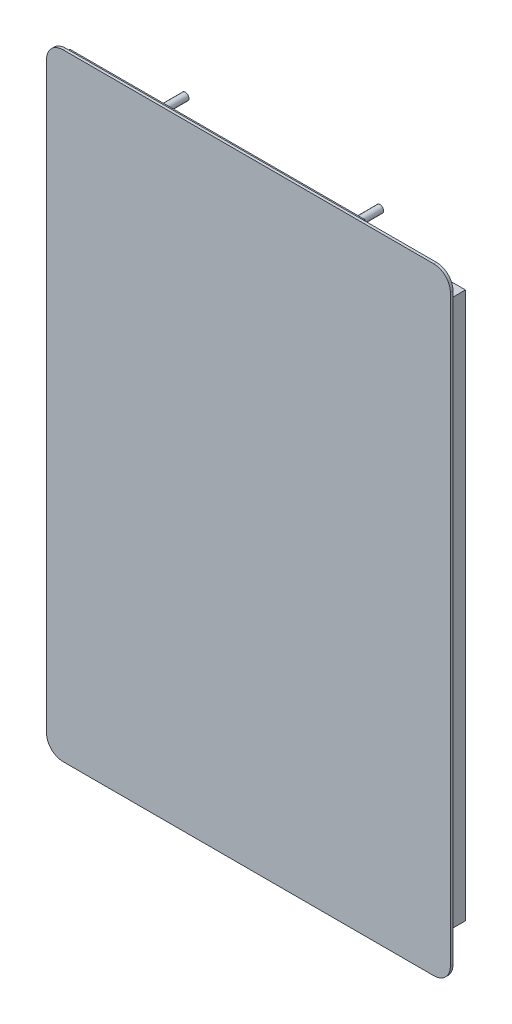
SolidWorks part; units mm, degrees
ref_plane "Front Plane" through (0, 0, 0) normal (0, 0, 1) x (1, 0, 0)
ref_plane "Top Plane" through (0, 0, 0) normal (0, 1, 0) x (1, 0, 0)
ref_plane "Right Plane" through (0, 0, 0) normal (1, 0, 0) x (0, 0, -1)
sketch "Sketch2" plane through (0, 0, 0) normal (0, 0, 1) x (1, 0, 0)
  line L1 (-76.67, -127.5) -> (76.67, -127.5)
  line L2 (-83.5, -120.67) -> (-83.5, 120.67)
  line L3 (-76.67, 127.5) -> (76.67, 127.5)
  line L4 (83.5, -120.67) -> (83.5, 120.67)
  line L5 (-83.5, -127.5) -> (83.5, 127.5) construction
  line L6 (-83.5, 127.5) -> (83.5, -127.5) construction
  arc A0 (76.67, 127.5) -> (83.5, 120.67) centre (76.67, 120.67) cw
  arc A1 (76.67, -127.5) -> (83.5, -120.67) centre (76.67, -120.67) ccw
  arc A2 (-76.67, -127.5) -> (-83.5, -120.67) centre (-76.67, -120.67) cw
  arc A3 (-76.67, 127.5) -> (-83.5, 120.67) centre (-76.67, 120.67) ccw
  point P0 (0, 0)
  dimension "D3" = 6.83
  dimension "D1" = 167
  dimension "D2" = 255
extrude "Boss-Extrude1" add sketch "Sketch2" along normal blind 1.1
sketch "Sketch3" plane through (0, 0, 0) normal (0, 0, -1) x (-1, 0, 0)
  line L0 (-76.67, 127.5) -> (76.67, 127.5) construction
  line L1 (-46.04, 127) -> (75.96, 127)
  line L2 (-46.04, 127) -> (-46.04, -127)
  line L3 (-46.04, -127) -> (75.96, -127)
  line L4 (75.96, 127) -> (75.96, -127)
  line L5 (83.5, 120.67) -> (83.5, -120.67) construction
  line L7 (76.67, -127.5) -> (-76.67, -127.5) construction
  point P4 (-48.9586, 122.3135)
  dimension "D1" = 0.5
  dimension "D2" = 7.54
  dimension "D3" = 122
  dimension "D4" = 0.5
extrude "Boss-Extrude2" add sketch "Sketch3" along normal blind 1
sketch "Sketch4" plane through (0, 0, 0) normal (0, 0, -1) x (-1, 0, 0)
  line L0 (0, 0) -> (-83.5, 0) construction
  line L1 (-83.5, -120.67) -> (-83.5, 120.67) construction
  line L2 (-46.04, 127) -> (-46.04, -127) construction
  line L3 (-78.04, 113) -> (-46.04, 113)
  line L4 (-78.04, 113) -> (-78.04, -113)
  line L5 (-78.04, -113) -> (-46.04, -113)
  line L6 (-46.04, 113) -> (-46.04, -113)
  line L7 (-78.04, 113) -> (-46.04, -113) construction
  line L8 (-78.04, -113) -> (-46.04, 113) construction
  point P5 (-62.04, 0)
  point P12 (-77.9097, -113.0417)
  dimension "D1" = 226
  dimension "D2" = 32
extrude "Boss-Extrude3" add sketch "Sketch4" along normal blind 10.6
sketch "Sketch5" plane through (0, 0, 0) normal (0, 0, -1) x (-1, 0, 0)
  line L0 (0, 0) -> (17.045, 0) construction
  line L1 (83.5, 120.67) -> (83.5, -120.67) construction
  line L2 (57.3, 104.9) -> (-23.21, 104.9) construction
  line L3 (57.3, 104.9) -> (57.3, -104.9) construction
  line L4 (57.3, -104.9) -> (-23.21, -104.9) construction
  line L5 (-23.21, 104.9) -> (-23.21, -104.9) construction
  line L6 (57.3, 104.9) -> (-23.21, -104.9) construction
  line L7 (57.3, -104.9) -> (-23.21, 104.9) construction
  line L8 (76.67, -127.5) -> (-76.67, -127.5) construction
  circle A0 centre (-23.21, -104.9) radius 1.5
  circle A1 centre (57.3, -104.9) radius 1.5
  circle A2 centre (57.3, 104.9) radius 1.5
  circle A3 centre (-23.21, 104.9) radius 1.5
  dimension "D4" = 3
  dimension "D1" = 26.2
  dimension "D2" = 22.6
  dimension "D3" = 80.51
extrude "Boss-Extrude4" add sketch "Sketch5" along normal offset from surface (30.1 mm away) 31.2 up to face at (0, 0, 1.1)
